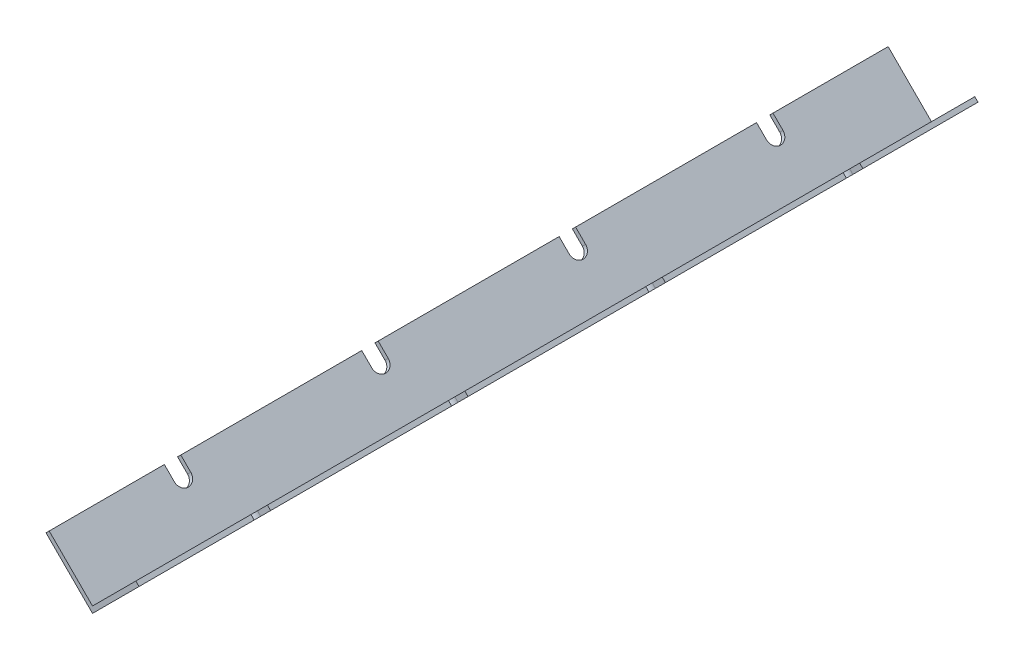
SolidWorks part; units mm, degrees
material "6061 Alloy"
ref_plane "Front Plane" through (0, 0, 0) normal (0, 0, 1) x (1, 0, 0)
ref_plane "Top Plane" through (0, 0, 0) normal (0, 1, 0) x (1, 0, 0)
ref_plane "Right Plane" through (0, 0, 0) normal (1, 0, 0) x (0, 0, -1)
sketch "Sketch1" plane through (0, 0, 0) normal (0, 0, 1) x (1, 0, 0)
  line L0 (0, 0) -> (-17.9605, 17.9605)
  line L1 (-17.9605, 17.9605) -> (-16.7257, 19.1953)
  line L2 (-16.7257, 19.1953) -> (0, 2.4696)
  line L3 (0, 2.4696) -> (16.7257, 19.1953)
  line L4 (16.7257, 19.1953) -> (17.9605, 17.9605)
  line L5 (17.9605, 17.9605) -> (0, 0)
  dimension "D1" = 1.7463
  dimension "D2" = 25.4
extrude "Boss-Extrude1" add sketch "Sketch1" along normal blind 323.85
sketch "Sketch3" plane through (0, 0, 0) normal (1, 0, 0) x (0, 0, -1)
  line L0 (-276.225, 16.2743) -> (-323.85, 16.2743) construction
  line L6 (-196.85, 19.1953) -> (-203.2, 19.1953)
  line L7 (-203.2, 19.1953) -> (-203.2, 16.2743)
  line L8 (-196.85, 16.2743) -> (-196.85, 19.1953)
  line L9 (-120.65, 19.1953) -> (-127, 19.1953)
  line L10 (-127, 19.1953) -> (-127, 16.2743)
  line L11 (-120.65, 16.2743) -> (-120.65, 19.1953)
  line L16 (-44.45, 19.1953) -> (-50.8, 19.1953)
  line L17 (-50.8, 19.1953) -> (-50.8, 16.2743)
  line L22 (-44.45, 16.2743) -> (-44.45, 19.1953)
  line L28 (-323.85, 0) -> (-323.85, 17.9605) construction
  line L29 (-276.225, 16.2743) -> (-200.025, 16.2743) construction
  line L30 (-279.4, 19.1953) -> (-279.4, 16.2743)
  line L31 (-323.85, 19.1953) -> (0, 19.1953) construction
  line L32 (-273.05, 16.2743) -> (-273.05, 19.1953)
  line L33 (-273.05, 19.1953) -> (-279.4, 19.1953)
  line L34 (-200.025, 16.2743) -> (-123.825, 16.2743) construction
  line L35 (-123.825, 16.2743) -> (-47.625, 16.2743) construction
  line L36 (-47.625, 16.2743) -> (0, 16.2743) construction
  line L37 (0, 0) -> (0, 17.9605) construction
  arc A0 (-279.4, 16.2743) -> (-273.05, 16.2743) centre (-276.225, 16.2743) ccw
  arc A1 (-203.2, 16.2743) -> (-196.85, 16.2743) centre (-200.025, 16.2743) ccw
  arc A2 (-127, 16.2743) -> (-120.65, 16.2743) centre (-123.825, 16.2743) ccw
  arc A3 (-50.8, 16.2743) -> (-44.45, 16.2743) centre (-47.625, 16.2743) ccw
  dimension "D1" = 76.2
  dimension "D2" = 6.096
  dimension "D4" = 6.35
extrude "Cut-Extrude2" cut sketch "Sketch3" against normal through all both and the other way through all
sketch "Sketch4" plane through (0, 0, 0) normal (0.7071, -0.7071, 0) x (0, 0, -1)
  line L0 (-279.4, 25.4) -> (-279.4, 19.954)
  line L1 (-273.05, 19.954) -> (-273.05, 25.4)
  line L17 (-273.05, 25.4) -> (-279.4, 25.4)
  line L21 (-203.2, 25.4) -> (-203.2, 19.954)
  line L22 (-196.85, 19.954) -> (-196.85, 25.4)
  line L23 (-196.85, 25.4) -> (-203.2, 25.4)
  line L24 (-127, 25.4) -> (-127, 19.954)
  line L25 (-120.65, 19.954) -> (-120.65, 25.4)
  line L26 (-120.65, 25.4) -> (-127, 25.4)
  line L27 (-50.8, 25.4) -> (-50.8, 19.954)
  line L28 (-44.45, 19.954) -> (-44.45, 25.4)
  line L29 (-44.45, 25.4) -> (-50.8, 25.4)
  line L30 (-50.8, 23.0153) -> (-50.8, 25.4) construction
  arc A0 (-279.4, 19.954) -> (-273.05, 19.954) centre (-276.225, 19.954) ccw
  arc A2 (-203.2, 19.954) -> (-196.85, 19.954) centre (-200.025, 19.954) ccw
  arc A5 (-127, 19.954) -> (-120.65, 19.954) centre (-123.825, 19.954) ccw
  arc A6 (-50.8, 19.954) -> (-44.45, 19.954) centre (-47.625, 19.954) ccw
  ellipse E3 centre (-276.225, 21.2691) end of major axis (-276.225, 25.7592) minor radius 3.175 (-279.4, 21.2691) -> (-273.05, 21.2691) ccw construction
  dimension "D1" = 4
extrude "Cut-Extrude3" cut sketch "Sketch4" against normal through all both and the other way through all
mirror "Mirror1" about plane through (0, 0, 0) normal (1, 0, 0) of "Cut-Extrude3"
